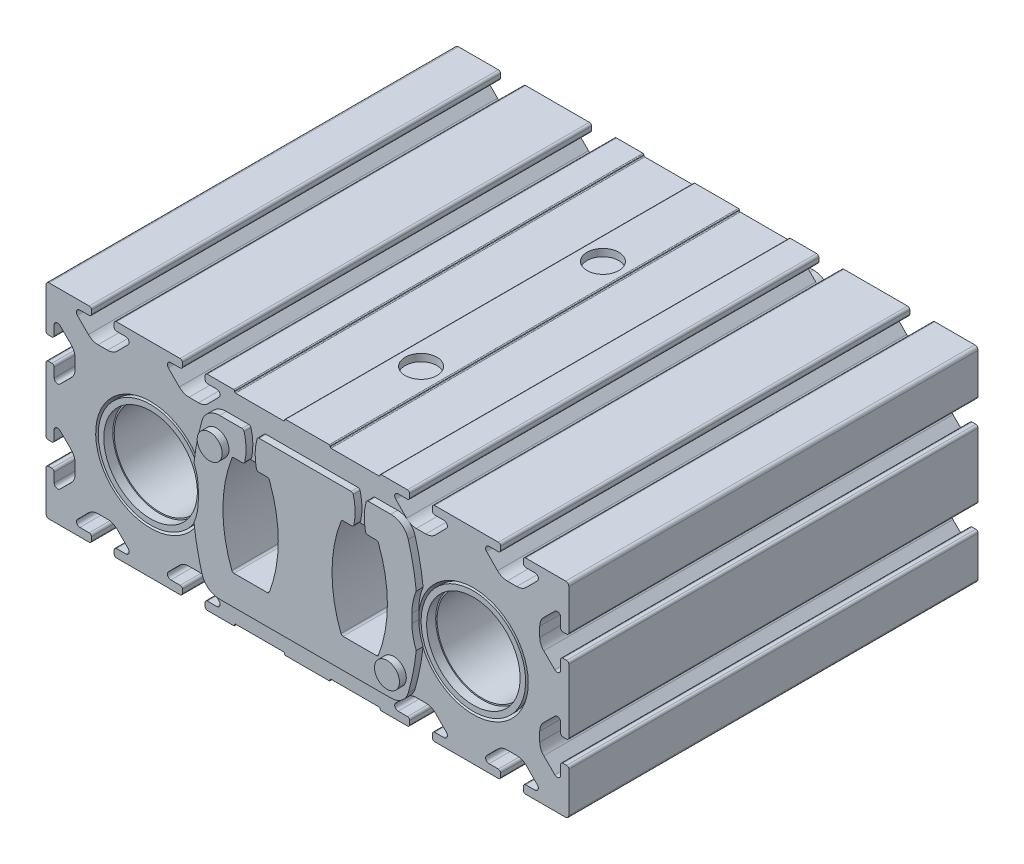
SolidWorks part; units mm, degrees
ref_plane "Front Plane" through (0, 0, 0) normal (0, 0, 1) x (1, 0, 0)
ref_plane "Top Plane" through (0, 0, 0) normal (0, 1, 0) x (1, 0, 0)
ref_plane "Right Plane" through (0, 0, 0) normal (1, 0, 0) x (0, 0, -1)
sketch "Sketch1" plane through (0, 0, 0) normal (0, 0, 1) x (1, 0, 0)
  line L0 (-56.8, -22.5) -> (-48, -22.5)
  line L1 (-47.5, -22) -> (-47.5, -21.2)
  line L2 (-48, -20.7) -> (-50.05, -20.7)
  line L3 (-50.5835, -19.4228) -> (-48.1808, -16.9914)
  line L4 (-46.0469, -16.1) -> (-43.9531, -16.1)
  line L5 (-41.8192, -16.9914) -> (-39.4165, -19.4228)
  line L6 (-39.95, -20.7) -> (-42, -20.7)
  line L7 (-42.5, -21.2) -> (-42.5, -22)
  line L8 (-42, -22.5) -> (-28, -22.5)
  line L9 (-27.5, -22) -> (-27.5, -21.2)
  line L10 (-28, -20.7) -> (-30.05, -20.7)
  line L11 (-30.5835, -19.4228) -> (-28.1808, -16.9914)
  line L12 (-26.0469, -16.1) -> (-23.9531, -16.1)
  line L13 (-21.8192, -16.9914) -> (-19.4165, -19.4228)
  line L14 (-19.95, -20.7) -> (-22, -20.7)
  line L15 (-22.5, -21.2) -> (-22.5, -22)
  line L16 (-22, -22.5) -> (-16.2, -22.5)
  line L17 (-16, -22.3) -> (-16, -22.2)
  line L18 (-15.8, -22) -> (-5.2, -22)
  line L19 (-5, -22.2) -> (-5, -22.3)
  line L20 (-4.8, -22.5) -> (4.8, -22.5)
  line L21 (5, -22.3) -> (5, -22.2)
  line L22 (5.2, -22) -> (15.8, -22)
  line L23 (16, -22.2) -> (16, -22.3)
  line L24 (16.2, -22.5) -> (22, -22.5)
  line L25 (22.5, -22) -> (22.5, -21.2)
  line L26 (22, -20.7) -> (19.95, -20.7)
  line L27 (19.4165, -19.4228) -> (21.8192, -16.9914)
  line L28 (23.9531, -16.1) -> (26.0469, -16.1)
  line L29 (28.1808, -16.9914) -> (30.5835, -19.4228)
  line L30 (30.05, -20.7) -> (28, -20.7)
  line L31 (27.5, -21.2) -> (27.5, -22)
  line L32 (28, -22.5) -> (42, -22.5)
  line L33 (42.5, -22) -> (42.5, -21.2)
  line L34 (42, -20.7) -> (39.95, -20.7)
  line L35 (39.4165, -19.4228) -> (41.8192, -16.9914)
  line L36 (43.9531, -16.1) -> (46.0469, -16.1)
  line L37 (48.1808, -16.9914) -> (50.5835, -19.4228)
  line L38 (50.05, -20.7) -> (48, -20.7)
  line L39 (47.5, -21.2) -> (47.5, -22)
  line L40 (48, -22.5) -> (56.8, -22.5)
  line L41 (57.5, -21.8) -> (57.5, -13)
  line L42 (57, -12.5) -> (56.2, -12.5)
  line L43 (55.7, -13) -> (55.7, -15.05)
  line L44 (54.4228, -15.5835) -> (51.9914, -13.1808)
  line L45 (51.1, -11.0469) -> (51.1, -8.9531)
  line L46 (51.9914, -6.8192) -> (54.4228, -4.4165)
  line L47 (55.7, -4.95) -> (55.7, -7)
  line L48 (56.2, -7.5) -> (57, -7.5)
  line L49 (57.5, -7) -> (57.5, 7)
  line L50 (57, 7.5) -> (56.2, 7.5)
  line L51 (55.7, 7) -> (55.7, 4.95)
  line L52 (54.4228, 4.4165) -> (51.9914, 6.8192)
  line L53 (51.1, 8.9531) -> (51.1, 11.0469)
  line L54 (51.9914, 13.1808) -> (54.4228, 15.5835)
  line L55 (55.7, 15.05) -> (55.7, 13)
  line L56 (56.2, 12.5) -> (57, 12.5)
  line L57 (57.5, 13) -> (57.5, 21.8)
  line L58 (56.8, 22.5) -> (48, 22.5)
  line L59 (47.5, 22) -> (47.5, 21.2)
  line L60 (48, 20.7) -> (50.05, 20.7)
  line L61 (50.5835, 19.4228) -> (48.1808, 16.9914)
  line L62 (46.0469, 16.1) -> (43.9531, 16.1)
  line L63 (41.8192, 16.9914) -> (39.4165, 19.4228)
  line L64 (39.95, 20.7) -> (42, 20.7)
  line L65 (42.5, 21.2) -> (42.5, 22)
  line L66 (42, 22.5) -> (28, 22.5)
  line L67 (27.5, 22) -> (27.5, 21.2)
  line L68 (28, 20.7) -> (30.05, 20.7)
  line L69 (30.5835, 19.4228) -> (28.1808, 16.9914)
  line L70 (26.0469, 16.1) -> (23.9531, 16.1)
  line L71 (21.8192, 16.9914) -> (19.4165, 19.4228)
  line L72 (19.95, 20.7) -> (22, 20.7)
  line L73 (22.5, 21.2) -> (22.5, 22)
  line L74 (22, 22.5) -> (16.2, 22.5)
  line L75 (16, 22.3) -> (16, 22.2)
  line L76 (15.8, 22) -> (5.2, 22)
  line L77 (5, 22.2) -> (5, 22.3)
  line L78 (4.8, 22.5) -> (-4.8, 22.5)
  line L79 (-5, 22.3) -> (-5, 22.2)
  line L80 (-5.2, 22) -> (-15.8, 22)
  line L81 (-16, 22.2) -> (-16, 22.3)
  line L82 (-16.2, 22.5) -> (-22, 22.5)
  line L83 (-22.5, 22) -> (-22.5, 21.2)
  line L84 (-22, 20.7) -> (-19.95, 20.7)
  line L85 (-19.4165, 19.4228) -> (-21.8192, 16.9914)
  line L86 (-23.9531, 16.1) -> (-26.0469, 16.1)
  line L87 (-28.1808, 16.9914) -> (-30.5835, 19.4228)
  line L88 (-30.05, 20.7) -> (-28, 20.7)
  line L89 (-27.5, 21.2) -> (-27.5, 22)
  line L90 (-28, 22.5) -> (-42, 22.5)
  line L91 (-42.5, 22) -> (-42.5, 21.2)
  line L92 (-42, 20.7) -> (-39.95, 20.7)
  line L93 (-39.4165, 19.4228) -> (-41.8192, 16.9914)
  line L94 (-43.9531, 16.1) -> (-46.0469, 16.1)
  line L95 (-48.1808, 16.9914) -> (-50.5835, 19.4228)
  line L96 (-50.05, 20.7) -> (-48, 20.7)
  line L97 (-47.5, 21.2) -> (-47.5, 22)
  line L98 (-48, 22.5) -> (-56.8, 22.5)
  line L99 (-57.5, 21.8) -> (-57.5, 13)
  line L100 (-57, 12.5) -> (-56.2, 12.5)
  line L101 (-55.7, 13) -> (-55.7, 15.05)
  line L102 (-54.4228, 15.5835) -> (-51.9914, 13.1808)
  line L103 (-51.1, 11.0469) -> (-51.1, 8.9531)
  line L104 (-51.9914, 6.8192) -> (-54.4228, 4.4165)
  line L105 (-55.7, 4.95) -> (-55.7, 7)
  line L106 (-56.2, 7.5) -> (-57, 7.5)
  line L107 (-57.5, 7) -> (-57.5, -7)
  line L108 (-57, -7.5) -> (-56.2, -7.5)
  line L109 (-55.7, -7) -> (-55.7, -4.95)
  line L110 (-54.4228, -4.4165) -> (-51.9914, -6.8192)
  line L111 (-51.1, -8.9531) -> (-51.1, -11.0469)
  line L112 (-51.9914, -13.1808) -> (-54.4228, -15.5835)
  line L113 (-55.7, -15.05) -> (-55.7, -13)
  line L114 (-56.2, -12.5) -> (-57, -12.5)
  line L115 (-57.5, -13) -> (-57.5, -21.8)
  line L116 (9.3425, -11) -> (16.6575, -11)
  line L117 (16.6575, 11) -> (9.3425, 11)
  line L118 (-14.6575, -11) -> (-7.3425, -11)
  line L119 (-7.3425, 11) -> (-14.6575, 11)
  arc A0 (-57.5, -21.8) -> (-56.8, -22.5) centre (-56.8, -21.8) ccw
  arc A1 (-48, -22.5) -> (-47.5, -22) centre (-48, -22) ccw
  arc A2 (-47.5, -21.2) -> (-48, -20.7) centre (-48, -21.2) ccw
  arc A3 (-50.05, -20.7) -> (-50.5835, -19.4228) centre (-50.05, -19.95) cw
  arc A4 (-48.1808, -16.9914) -> (-46.0469, -16.1) centre (-46.0469, -19.1) cw
  arc A5 (-43.9531, -16.1) -> (-41.8192, -16.9914) centre (-43.9531, -19.1) cw
  arc A6 (-39.4165, -19.4228) -> (-39.95, -20.7) centre (-39.95, -19.95) cw
  arc A7 (-42, -20.7) -> (-42.5, -21.2) centre (-42, -21.2) ccw
  arc A8 (-42.5, -22) -> (-42, -22.5) centre (-42, -22) ccw
  arc A9 (-28, -22.5) -> (-27.5, -22) centre (-28, -22) ccw
  arc A10 (-27.5, -21.2) -> (-28, -20.7) centre (-28, -21.2) ccw
  arc A11 (-30.05, -20.7) -> (-30.5835, -19.4228) centre (-30.05, -19.95) cw
  arc A12 (-28.1808, -16.9914) -> (-26.0469, -16.1) centre (-26.0469, -19.1) cw
  arc A13 (-23.9531, -16.1) -> (-21.8192, -16.9914) centre (-23.9531, -19.1) cw
  arc A14 (-19.4165, -19.4228) -> (-19.95, -20.7) centre (-19.95, -19.95) cw
  arc A15 (-22, -20.7) -> (-22.5, -21.2) centre (-22, -21.2) ccw
  arc A16 (-22.5, -22) -> (-22, -22.5) centre (-22, -22) ccw
  arc A17 (-16.2, -22.5) -> (-16, -22.3) centre (-16.2, -22.3) ccw
  arc A18 (-16, -22.2) -> (-15.8, -22) centre (-15.8, -22.2) cw
  arc A19 (-5.2, -22) -> (-5, -22.2) centre (-5.2, -22.2) cw
  arc A20 (-5, -22.3) -> (-4.8, -22.5) centre (-4.8, -22.3) ccw
  arc A21 (4.8, -22.5) -> (5, -22.3) centre (4.8, -22.3) ccw
  arc A22 (5, -22.2) -> (5.2, -22) centre (5.2, -22.2) cw
  arc A23 (15.8, -22) -> (16, -22.2) centre (15.8, -22.2) cw
  arc A24 (16, -22.3) -> (16.2, -22.5) centre (16.2, -22.3) ccw
  arc A25 (22, -22.5) -> (22.5, -22) centre (22, -22) ccw
  arc A26 (22.5, -21.2) -> (22, -20.7) centre (22, -21.2) ccw
  arc A27 (19.95, -20.7) -> (19.4165, -19.4228) centre (19.95, -19.95) cw
  arc A28 (21.8192, -16.9914) -> (23.9531, -16.1) centre (23.9531, -19.1) cw
  arc A29 (26.0469, -16.1) -> (28.1808, -16.9914) centre (26.0469, -19.1) cw
  arc A30 (30.5835, -19.4228) -> (30.05, -20.7) centre (30.05, -19.95) cw
  arc A31 (28, -20.7) -> (27.5, -21.2) centre (28, -21.2) ccw
  arc A32 (27.5, -22) -> (28, -22.5) centre (28, -22) ccw
  arc A33 (42, -22.5) -> (42.5, -22) centre (42, -22) ccw
  arc A34 (42.5, -21.2) -> (42, -20.7) centre (42, -21.2) ccw
  arc A35 (39.95, -20.7) -> (39.4165, -19.4228) centre (39.95, -19.95) cw
  arc A36 (41.8192, -16.9914) -> (43.9531, -16.1) centre (43.9531, -19.1) cw
  arc A37 (46.0469, -16.1) -> (48.1808, -16.9914) centre (46.0469, -19.1) cw
  arc A38 (50.5835, -19.4228) -> (50.05, -20.7) centre (50.05, -19.95) cw
  arc A39 (48, -20.7) -> (47.5, -21.2) centre (48, -21.2) ccw
  arc A40 (47.5, -22) -> (48, -22.5) centre (48, -22) ccw
  arc A41 (56.8, -22.5) -> (57.5, -21.8) centre (56.8, -21.8) ccw
  arc A42 (57.5, -13) -> (57, -12.5) centre (57, -13) ccw
  arc A43 (56.2, -12.5) -> (55.7, -13) centre (56.2, -13) ccw
  arc A44 (55.7, -15.05) -> (54.4228, -15.5835) centre (54.95, -15.05) cw
  arc A45 (51.9914, -13.1808) -> (51.1, -11.0469) centre (54.1, -11.0469) cw
  arc A46 (51.1, -8.9531) -> (51.9914, -6.8192) centre (54.1, -8.9531) cw
  arc A47 (54.4228, -4.4165) -> (55.7, -4.95) centre (54.95, -4.95) cw
  arc A48 (55.7, -7) -> (56.2, -7.5) centre (56.2, -7) ccw
  arc A49 (57, -7.5) -> (57.5, -7) centre (57, -7) ccw
  arc A50 (57.5, 7) -> (57, 7.5) centre (57, 7) ccw
  arc A51 (56.2, 7.5) -> (55.7, 7) centre (56.2, 7) ccw
  arc A52 (55.7, 4.95) -> (54.4228, 4.4165) centre (54.95, 4.95) cw
  arc A53 (51.9914, 6.8192) -> (51.1, 8.9531) centre (54.1, 8.9531) cw
  arc A54 (51.1, 11.0469) -> (51.9914, 13.1808) centre (54.1, 11.0469) cw
  arc A55 (54.4228, 15.5835) -> (55.7, 15.05) centre (54.95, 15.05) cw
  arc A56 (55.7, 13) -> (56.2, 12.5) centre (56.2, 13) ccw
  arc A57 (57, 12.5) -> (57.5, 13) centre (57, 13) ccw
  arc A58 (57.5, 21.8) -> (56.8, 22.5) centre (56.8, 21.8) ccw
  arc A59 (48, 22.5) -> (47.5, 22) centre (48, 22) ccw
  arc A60 (47.5, 21.2) -> (48, 20.7) centre (48, 21.2) ccw
  arc A61 (50.05, 20.7) -> (50.5835, 19.4228) centre (50.05, 19.95) cw
  arc A62 (48.1808, 16.9914) -> (46.0469, 16.1) centre (46.0469, 19.1) cw
  arc A63 (43.9531, 16.1) -> (41.8192, 16.9914) centre (43.9531, 19.1) cw
  arc A64 (39.4165, 19.4228) -> (39.95, 20.7) centre (39.95, 19.95) cw
  arc A65 (42, 20.7) -> (42.5, 21.2) centre (42, 21.2) ccw
  arc A66 (42.5, 22) -> (42, 22.5) centre (42, 22) ccw
  arc A67 (28, 22.5) -> (27.5, 22) centre (28, 22) ccw
  arc A68 (27.5, 21.2) -> (28, 20.7) centre (28, 21.2) ccw
  arc A69 (30.05, 20.7) -> (30.5835, 19.4228) centre (30.05, 19.95) cw
  arc A70 (28.1808, 16.9914) -> (26.0469, 16.1) centre (26.0469, 19.1) cw
  arc A71 (23.9531, 16.1) -> (21.8192, 16.9914) centre (23.9531, 19.1) cw
  arc A72 (19.4165, 19.4228) -> (19.95, 20.7) centre (19.95, 19.95) cw
  arc A73 (22, 20.7) -> (22.5, 21.2) centre (22, 21.2) ccw
  arc A74 (22.5, 22) -> (22, 22.5) centre (22, 22) ccw
  arc A75 (16.2, 22.5) -> (16, 22.3) centre (16.2, 22.3) ccw
  arc A76 (16, 22.2) -> (15.8, 22) centre (15.8, 22.2) cw
  arc A77 (5.2, 22) -> (5, 22.2) centre (5.2, 22.2) cw
  arc A78 (5, 22.3) -> (4.8, 22.5) centre (4.8, 22.3) ccw
  arc A79 (-4.8, 22.5) -> (-5, 22.3) centre (-4.8, 22.3) ccw
  arc A80 (-5, 22.2) -> (-5.2, 22) centre (-5.2, 22.2) cw
  arc A81 (-15.8, 22) -> (-16, 22.2) centre (-15.8, 22.2) cw
  arc A82 (-16, 22.3) -> (-16.2, 22.5) centre (-16.2, 22.3) ccw
  arc A83 (-22, 22.5) -> (-22.5, 22) centre (-22, 22) ccw
  arc A84 (-22.5, 21.2) -> (-22, 20.7) centre (-22, 21.2) ccw
  arc A85 (-19.95, 20.7) -> (-19.4165, 19.4228) centre (-19.95, 19.95) cw
  arc A86 (-21.8192, 16.9914) -> (-23.9531, 16.1) centre (-23.9531, 19.1) cw
  arc A87 (-26.0469, 16.1) -> (-28.1808, 16.9914) centre (-26.0469, 19.1) cw
  arc A88 (-30.5835, 19.4228) -> (-30.05, 20.7) centre (-30.05, 19.95) cw
  arc A89 (-28, 20.7) -> (-27.5, 21.2) centre (-28, 21.2) ccw
  arc A90 (-27.5, 22) -> (-28, 22.5) centre (-28, 22) ccw
  arc A91 (-42, 22.5) -> (-42.5, 22) centre (-42, 22) ccw
  arc A92 (-42.5, 21.2) -> (-42, 20.7) centre (-42, 21.2) ccw
  arc A93 (-39.95, 20.7) -> (-39.4165, 19.4228) centre (-39.95, 19.95) cw
  arc A94 (-41.8192, 16.9914) -> (-43.9531, 16.1) centre (-43.9531, 19.1) cw
  arc A95 (-46.0469, 16.1) -> (-48.1808, 16.9914) centre (-46.0469, 19.1) cw
  arc A96 (-50.5835, 19.4228) -> (-50.05, 20.7) centre (-50.05, 19.95) cw
  arc A97 (-48, 20.7) -> (-47.5, 21.2) centre (-48, 21.2) ccw
  arc A98 (-47.5, 22) -> (-48, 22.5) centre (-48, 22) ccw
  arc A99 (-56.8, 22.5) -> (-57.5, 21.8) centre (-56.8, 21.8) ccw
  arc A100 (-57.5, 13) -> (-57, 12.5) centre (-57, 13) ccw
  arc A101 (-56.2, 12.5) -> (-55.7, 13) centre (-56.2, 13) ccw
  arc A102 (-55.7, 15.05) -> (-54.4228, 15.5835) centre (-54.95, 15.05) cw
  arc A103 (-51.9914, 13.1808) -> (-51.1, 11.0469) centre (-54.1, 11.0469) cw
  arc A104 (-51.1, 8.9531) -> (-51.9914, 6.8192) centre (-54.1, 8.9531) cw
  arc A105 (-54.4228, 4.4165) -> (-55.7, 4.95) centre (-54.95, 4.95) cw
  arc A106 (-55.7, 7) -> (-56.2, 7.5) centre (-56.2, 7) ccw
  arc A107 (-57, 7.5) -> (-57.5, 7) centre (-57, 7) ccw
  arc A108 (-57.5, -7) -> (-57, -7.5) centre (-57, -7) ccw
  arc A109 (-56.2, -7.5) -> (-55.7, -7) centre (-56.2, -7) ccw
  arc A110 (-55.7, -4.95) -> (-54.4228, -4.4165) centre (-54.95, -4.95) cw
  arc A111 (-51.9914, -6.8192) -> (-51.1, -8.9531) centre (-54.1, -8.9531) cw
  arc A112 (-51.1, -11.0469) -> (-51.9914, -13.1808) centre (-54.1, -11.0469) cw
  arc A113 (-54.4228, -15.5835) -> (-55.7, -15.05) centre (-54.95, -15.05) cw
  arc A114 (-55.7, -13) -> (-56.2, -12.5) centre (-56.2, -13) ccw
  arc A115 (-57, -12.5) -> (-57.5, -13) centre (-57, -13) ccw
  arc A116 (8.8752, 10.678) -> (8.8752, -10.678) centre (36.9106, 0) ccw
  arc A117 (8.8752, -10.678) -> (9.3425, -11) centre (9.3425, -10.5) ccw
  arc A118 (16.6575, -11) -> (17.1248, -10.678) centre (16.6575, -10.5) ccw
  arc A119 (17.1248, -10.678) -> (17.1248, 10.678) centre (-10.9106, 0) ccw
  arc A120 (17.1248, 10.678) -> (16.6575, 11) centre (16.6575, 10.5) ccw
  arc A121 (9.3425, 11) -> (8.8752, 10.678) centre (9.3425, 10.5) ccw
  arc A122 (-15.1248, 10.678) -> (-15.1248, -10.678) centre (12.9106, 0) ccw
  arc A123 (-15.1248, -10.678) -> (-14.6575, -11) centre (-14.6575, -10.5) ccw
  arc A124 (-7.3425, -11) -> (-6.8752, -10.678) centre (-7.3425, -10.5) ccw
  arc A125 (-6.8752, -10.678) -> (-6.8752, 10.678) centre (-34.9106, 0) ccw
  arc A126 (-6.8752, 10.678) -> (-7.3425, 11) centre (-7.3425, 10.5) ccw
  arc A127 (-14.6575, 11) -> (-15.1248, 10.678) centre (-14.6575, 10.5) ccw
extrude "Boss-Extrude1" add sketch "Sketch1" against normal blind 90
ref_plane "Plane4" through (0, -1, 0) normal (0, 1, 0) x (1, 0, 0)
sketch "Sketch2" plane through (0, -1, 0) normal (0, 1, 0) x (1, 0, 0)
  line L0 (-34.5, 90) -> (-22.4226, 90)
  line L1 (-22.4226, 90) -> (-23, 89)
  line L2 (-23, 89) -> (-23, 1)
  line L3 (-23, 1) -> (-22.4226, 0)
  line L4 (-22.4226, 0) -> (-34.5, 0)
  line L5 (-34.5, 0) -> (-34.5, 90)
  line L6 (-34.5, 0) -> (-34.5, 90) construction
revolve "Cut-Revolve1" cut sketch "Sketch2" angle 360 about L6 reverse direction yes
sketch "Sketch3" plane through (0, -1, 0) normal (0, 1, 0) x (1, 0, 0)
  line L0 (36.5, 90) -> (48.5774, 90)
  line L1 (48.5774, 90) -> (48, 89)
  line L2 (48, 89) -> (48, 1)
  line L3 (48, 1) -> (48.5774, 0)
  line L4 (48.5774, 0) -> (36.5, 0)
  line L5 (36.5, 0) -> (36.5, 90)
  line L6 (36.5, 0) -> (36.5, 90) construction
revolve "Cut-Revolve2" cut sketch "Sketch3" angle 360 about L6 reverse direction yes
sketch "Sketch4" plane through (0, -1, 0) normal (0, 1, 0) x (1, 0, 0)
  line L0 (-24.5, 2) -> (-24.21, 2)
  line L1 (-24.21, 2) -> (-24.21, 0)
  line L2 (-24.21, 0) -> (-23, 0)
  line L3 (-23, 0) -> (-23, 24.2)
  line L4 (-23, 24.2) -> (-23.4619, 25)
  line L5 (-23.4619, 25) -> (-24.5, 25)
  line L6 (-24.5, 25) -> (-24.5, 2)
  line L7 (-34.5, 0) -> (-34.5, 25) construction
revolve "Revolve1" add sketch "Sketch4" angle 360 about L7 reverse direction yes
sketch "Sketch5" plane through (0, -1, 0) normal (0, 1, 0) x (1, 0, 0)
  line L0 (46.5, 2) -> (46.79, 2)
  line L1 (46.79, 2) -> (46.79, 0)
  line L2 (46.79, 0) -> (48, 0)
  line L3 (48, 0) -> (48, 24.2)
  line L4 (48, 24.2) -> (47.5381, 25)
  line L5 (47.5381, 25) -> (46.5, 25)
  line L6 (46.5, 25) -> (46.5, 2)
  line L7 (36.5, 0) -> (36.5, 25) construction
revolve "Revolve2" add sketch "Sketch5" angle 360 about L7 reverse direction yes
sketch "Sketch6" plane through (0, -1, 0) normal (0, 1, 0) x (1, 0, 0)
  line L0 (46.5, 88) -> (46.5, 65)
  line L1 (46.5, 65) -> (47.5381, 65)
  line L2 (47.5381, 65) -> (48, 65.8)
  line L3 (48, 65.8) -> (48, 90)
  line L4 (48, 90) -> (46.79, 90)
  line L5 (46.79, 90) -> (46.79, 88)
  line L6 (46.79, 88) -> (46.5, 88)
  line L7 (36.5, 65) -> (36.5, 90) construction
revolve "Revolve3" add sketch "Sketch6" angle 360 about L7 reverse direction yes
sketch "Sketch7" plane through (0, -1, 0) normal (0, 1, 0) x (1, 0, 0)
  line L0 (-24.5, 88) -> (-24.5, 65)
  line L1 (-24.5, 65) -> (-23.4619, 65)
  line L2 (-23.4619, 65) -> (-23, 65.8)
  line L3 (-23, 65.8) -> (-23, 90)
  line L4 (-23, 90) -> (-24.21, 90)
  line L5 (-24.21, 90) -> (-24.21, 88)
  line L6 (-24.21, 88) -> (-24.5, 88)
  line L7 (-34.5, 65) -> (-34.5, 90) construction
revolve "Revolve4" add sketch "Sketch7" angle 360 about L7 reverse direction yes
sketch "Sketch8" plane through (0, 0, 0) normal (0, 0, 1) x (1, 0, 0)
  line L0 (-22.5, 1) -> (-22.5, -1)
  line L1 (-17.8333, -17.5) -> (19.8333, -17.5)
  line L2 (24.5, -1) -> (24.5, 1)
  line L3 (19.8333, 17.5) -> (14.8982, 17.5)
  line L4 (14.775, 11) -> (16.6575, 11)
  line L5 (16.6575, -11) -> (9.3425, -11)
  line L6 (9.3425, 11) -> (11.225, 11)
  line L7 (11.1018, 17.5) -> (-9.1018, 17.5)
  line L8 (-9.225, 11) -> (-7.3425, 11)
  line L9 (-7.3425, -11) -> (-14.6575, -11)
  line L10 (-14.6575, 11) -> (-12.775, 11)
  line L11 (-12.8982, 17.5) -> (-17.8333, 17.5)
  arc A0 (-23.4435, 5.6642) -> (-22.5, 1) centre (-34.5, 1) cw
  arc A1 (-22.5, -1) -> (-23.4435, -5.6642) centre (-34.5, -1) cw
  arc A2 (-23.4435, -5.6642) -> (-21.6752, -14.6134) centre (28.75, 0) ccw
  arc A3 (-21.6752, -14.6134) -> (-17.8333, -17.5) centre (-17.8333, -13.5) ccw
  arc A4 (19.8333, -17.5) -> (23.6752, -14.6134) centre (19.8333, -13.5) ccw
  arc A5 (23.6752, -14.6134) -> (25.4435, -5.6642) centre (-26.75, 0) ccw
  arc A6 (25.4435, -5.6642) -> (24.5, -1) centre (36.5, -1) cw
  arc A7 (24.5, 1) -> (25.4435, 5.6642) centre (36.5, 1) cw
  arc A8 (25.4435, 5.6642) -> (23.6752, 14.6134) centre (-26.75, 0) ccw
  arc A9 (23.6752, 14.6134) -> (19.8333, 17.5) centre (19.8333, 13.5) ccw
  arc A10 (14.8982, 17.5) -> (14.4155, 17.1304) centre (14.8982, 17) ccw
  arc A11 (14.4155, 17.1304) -> (14.287, 11.3913) centre (26, 14) ccw
  arc A12 (14.287, 11.3913) -> (14.775, 11) centre (14.775, 11.5) ccw
  arc A13 (16.6575, 11) -> (17.1248, 10.678) centre (16.6575, 10.5) cw
  arc A14 (17.1248, 10.678) -> (17.1248, -10.678) centre (-10.9106, 0) cw
  arc A15 (17.1248, -10.678) -> (16.6575, -11) centre (16.6575, -10.5) cw
  arc A16 (9.3425, -11) -> (8.8752, -10.678) centre (9.3425, -10.5) cw
  arc A17 (8.8752, -10.678) -> (8.8752, 10.678) centre (36.9106, 0) cw
  arc A18 (8.8752, 10.678) -> (9.3425, 11) centre (9.3425, 10.5) cw
  arc A19 (11.225, 11) -> (11.713, 11.3913) centre (11.225, 11.5) ccw
  arc A20 (11.713, 11.3913) -> (11.5845, 17.1304) centre (0, 14) ccw
  arc A21 (11.5845, 17.1304) -> (11.1018, 17.5) centre (11.1018, 17) ccw
  arc A22 (-9.1018, 17.5) -> (-9.5845, 17.1304) centre (-9.1018, 17) ccw
  arc A23 (-9.5845, 17.1304) -> (-9.713, 11.3913) centre (2, 14) ccw
  arc A24 (-9.713, 11.3913) -> (-9.225, 11) centre (-9.225, 11.5) ccw
  arc A25 (-7.3425, 11) -> (-6.8752, 10.678) centre (-7.3425, 10.5) cw
  arc A26 (-6.8752, 10.678) -> (-6.8752, -10.678) centre (-34.9106, 0) cw
  arc A27 (-6.8752, -10.678) -> (-7.3425, -11) centre (-7.3425, -10.5) cw
  arc A28 (-14.6575, -11) -> (-15.1248, -10.678) centre (-14.6575, -10.5) cw
  arc A29 (-15.1248, -10.678) -> (-15.1248, 10.678) centre (12.9106, 0) cw
  arc A30 (-15.1248, 10.678) -> (-14.6575, 11) centre (-14.6575, 10.5) cw
  arc A31 (-12.775, 11) -> (-12.287, 11.3913) centre (-12.775, 11.5) ccw
  arc A32 (-12.287, 11.3913) -> (-12.4155, 17.1304) centre (-24, 14) ccw
  arc A33 (-12.4155, 17.1304) -> (-12.8982, 17.5) centre (-12.8982, 17) ccw
  arc A34 (-17.8333, 17.5) -> (-21.6752, 14.6134) centre (-17.8333, 13.5) ccw
  arc A35 (-21.6752, 14.6134) -> (-23.4435, 5.6642) centre (28.75, 0) ccw
  circle A36 centre (20.5, -12) radius 1.5
  circle A37 centre (-18.5, 12) radius 1.5
extrude "Boss-Extrude2" add sketch "Sketch8" along normal blind 1.5
ref_plane "Plane5" through (0, 0, -90) normal (0, 0, 1) x (1, 0, 0)
sketch "Sketch9" plane through (0, 0, -90) normal (0, 0, 1) x (1, 0, 0)
  line L0 (-22.5, 1) -> (-22.5, -1)
  line L1 (-17.8333, -17.5) -> (19.8333, -17.5)
  line L2 (24.5, -1) -> (24.5, 1)
  line L3 (19.8333, 17.5) -> (14.8982, 17.5)
  line L4 (14.775, 11) -> (16.6575, 11)
  line L5 (16.6575, -11) -> (9.3425, -11)
  line L6 (9.3425, 11) -> (11.225, 11)
  line L7 (11.1018, 17.5) -> (-9.1018, 17.5)
  line L8 (-9.225, 11) -> (-7.3425, 11)
  line L9 (-7.3425, -11) -> (-14.6575, -11)
  line L10 (-14.6575, 11) -> (-12.775, 11)
  line L11 (-12.8982, 17.5) -> (-17.8333, 17.5)
  arc A0 (-23.4435, 5.6642) -> (-22.5, 1) centre (-34.5, 1) cw
  arc A1 (-22.5, -1) -> (-23.4435, -5.6642) centre (-34.5, -1) cw
  arc A2 (-23.4435, -5.6642) -> (-21.6752, -14.6134) centre (28.75, 0) ccw
  arc A3 (-21.6752, -14.6134) -> (-17.8333, -17.5) centre (-17.8333, -13.5) ccw
  arc A4 (19.8333, -17.5) -> (23.6752, -14.6134) centre (19.8333, -13.5) ccw
  arc A5 (23.6752, -14.6134) -> (25.4435, -5.6642) centre (-26.75, 0) ccw
  arc A6 (25.4435, -5.6642) -> (24.5, -1) centre (36.5, -1) cw
  arc A7 (24.5, 1) -> (25.4435, 5.6642) centre (36.5, 1) cw
  arc A8 (25.4435, 5.6642) -> (23.6752, 14.6134) centre (-26.75, 0) ccw
  arc A9 (23.6752, 14.6134) -> (19.8333, 17.5) centre (19.8333, 13.5) ccw
  arc A10 (14.8982, 17.5) -> (14.4155, 17.1304) centre (14.8982, 17) ccw
  arc A11 (14.4155, 17.1304) -> (14.287, 11.3913) centre (26, 14) ccw
  arc A12 (14.287, 11.3913) -> (14.775, 11) centre (14.775, 11.5) ccw
  arc A13 (16.6575, 11) -> (17.1248, 10.678) centre (16.6575, 10.5) cw
  arc A14 (17.1248, 10.678) -> (17.1248, -10.678) centre (-10.9106, 0) cw
  arc A15 (17.1248, -10.678) -> (16.6575, -11) centre (16.6575, -10.5) cw
  arc A16 (9.3425, -11) -> (8.8752, -10.678) centre (9.3425, -10.5) cw
  arc A17 (8.8752, -10.678) -> (8.8752, 10.678) centre (36.9106, 0) cw
  arc A18 (8.8752, 10.678) -> (9.3425, 11) centre (9.3425, 10.5) cw
  arc A19 (11.225, 11) -> (11.713, 11.3913) centre (11.225, 11.5) ccw
  arc A20 (11.713, 11.3913) -> (11.5845, 17.1304) centre (0, 14) ccw
  arc A21 (11.5845, 17.1304) -> (11.1018, 17.5) centre (11.1018, 17) ccw
  arc A22 (-9.1018, 17.5) -> (-9.5845, 17.1304) centre (-9.1018, 17) ccw
  arc A23 (-9.5845, 17.1304) -> (-9.713, 11.3913) centre (2, 14) ccw
  arc A24 (-9.713, 11.3913) -> (-9.225, 11) centre (-9.225, 11.5) ccw
  arc A25 (-7.3425, 11) -> (-6.8752, 10.678) centre (-7.3425, 10.5) cw
  arc A26 (-6.8752, 10.678) -> (-6.8752, -10.678) centre (-34.9106, 0) cw
  arc A27 (-6.8752, -10.678) -> (-7.3425, -11) centre (-7.3425, -10.5) cw
  arc A28 (-14.6575, -11) -> (-15.1248, -10.678) centre (-14.6575, -10.5) cw
  arc A29 (-15.1248, -10.678) -> (-15.1248, 10.678) centre (12.9106, 0) cw
  arc A30 (-15.1248, 10.678) -> (-14.6575, 11) centre (-14.6575, 10.5) cw
  arc A31 (-12.775, 11) -> (-12.287, 11.3913) centre (-12.775, 11.5) ccw
  arc A32 (-12.287, 11.3913) -> (-12.4155, 17.1304) centre (-24, 14) ccw
  arc A33 (-12.4155, 17.1304) -> (-12.8982, 17.5) centre (-12.8982, 17) ccw
  arc A34 (-17.8333, 17.5) -> (-21.6752, 14.6134) centre (-17.8333, 13.5) ccw
  arc A35 (-21.6752, 14.6134) -> (-23.4435, 5.6642) centre (28.75, 0) ccw
  circle A36 centre (20.5, -12) radius 1.5
  circle A37 centre (-18.5, 12) radius 1.5
extrude "Boss-Extrude3" add sketch "Sketch9" against normal blind 1.5
ref_plane "Plane6" through (-18.5, 0, 0) normal (1, 0, 0) x (0, 0, -1)
sketch "Sketch10" plane through (-18.5, 0, 0) normal (1, 0, 0) x (0, 0, -1)
  line L0 (74.4, 12) -> (74.4, 12.5)
  line L1 (74.4, 12.5) -> (74.9, 13)
  line L2 (74.9, 13) -> (77, 13)
  line L3 (77, 13) -> (77, 13.1)
  line L4 (77, 13.1) -> (77.5, 13.6)
  line L5 (77.5, 13.6) -> (91.5, 13.6)
  line L6 (91.5, 13.6) -> (91.5, 14.75)
  line L7 (91.5, 14.75) -> (93, 14.75)
  line L8 (93, 14.75) -> (93, 12)
  line L9 (93, 12) -> (74.4, 12)
  line L10 (93, 12) -> (74.4, 12) construction
revolve "Revolve5" add sketch "Sketch10" angle 360 about L10 reverse direction yes
sketch "Sketch11" plane through (-18.5, 0, 0) normal (1, 0, 0) x (0, 0, -1)
  line L0 (-3, 12) -> (-3, 14.75)
  line L1 (-3, 14.75) -> (-1.5, 14.75)
  line L2 (-1.5, 14.75) -> (-1.5, 13.6)
  line L3 (-1.5, 13.6) -> (12.5, 13.6)
  line L4 (12.5, 13.6) -> (13, 13.1)
  line L5 (13, 13.1) -> (13, 13)
  line L6 (13, 13) -> (15.1, 13)
  line L7 (15.1, 13) -> (15.6, 12.5)
  line L8 (15.6, 12.5) -> (15.6, 12)
  line L9 (15.6, 12) -> (-3, 12)
  line L10 (15.6, 12) -> (-3, 12) construction
revolve "Revolve6" add sketch "Sketch11" angle 360 about L10 reverse direction yes
ref_plane "Plane7" through (20.5, 0, 0) normal (1, 0, 0) x (0, 0, -1)
sketch "Sketch12" plane through (20.5, 0, 0) normal (1, 0, 0) x (0, 0, -1)
  line L0 (-3, -12) -> (-3, -9.25)
  line L1 (-3, -9.25) -> (-1.5, -9.25)
  line L2 (-1.5, -9.25) -> (-1.5, -10.4)
  line L3 (-1.5, -10.4) -> (12.5, -10.4)
  line L4 (12.5, -10.4) -> (13, -10.9)
  line L5 (13, -10.9) -> (13, -11)
  line L6 (13, -11) -> (15.1, -11)
  line L7 (15.1, -11) -> (15.6, -11.5)
  line L8 (15.6, -11.5) -> (15.6, -12)
  line L9 (15.6, -12) -> (-3, -12)
  line L10 (15.6, -12) -> (-3, -12) construction
revolve "Revolve7" add sketch "Sketch12" angle 360 about L10 reverse direction yes
sketch "Sketch13" plane through (20.5, 0, 0) normal (1, 0, 0) x (0, 0, -1)
  line L0 (74.4, -12) -> (74.4, -11.5)
  line L1 (74.4, -11.5) -> (74.9, -11)
  line L2 (74.9, -11) -> (77, -11)
  line L3 (77, -11) -> (77, -10.9)
  line L4 (77, -10.9) -> (77.5, -10.4)
  line L5 (77.5, -10.4) -> (91.5, -10.4)
  line L6 (91.5, -10.4) -> (91.5, -9.25)
  line L7 (91.5, -9.25) -> (93, -9.25)
  line L8 (93, -9.25) -> (93, -12)
  line L9 (93, -12) -> (74.4, -12)
  line L10 (93, -12) -> (74.4, -12) construction
revolve "Revolve8" add sketch "Sketch13" angle 360 about L10 reverse direction yes
sketch "Sketch14" plane through (0, 0, 0) normal (1, 0, 0) x (0, 0, -1)
  line L0 (25, 22.5) -> (28.5, 22.5)
  line L1 (28.5, 22.5) -> (28.5, 20.9)
  line L2 (28.5, 20.9) -> (25, 20.9)
  line L3 (25, 20.9) -> (25, 22.5)
  line L4 (25, 20.9) -> (25, 22.5) construction
revolve "Cut-Revolve3" cut sketch "Sketch14" angle 360 about L4 reverse direction yes
sketch "Sketch15" plane through (0, 0, 0) normal (1, 0, 0) x (0, 0, -1)
  line L0 (65, 22.5) -> (68.5, 22.5)
  line L1 (68.5, 22.5) -> (68.5, 20.9)
  line L2 (68.5, 20.9) -> (65, 20.9)
  line L3 (65, 20.9) -> (65, 22.5)
  line L4 (65, 20.9) -> (65, 22.5) construction
revolve "Cut-Revolve4" cut sketch "Sketch15" angle 360 about L4 reverse direction yes
sketch "Sketch16" plane through (0, 0, 0) normal (0, 1, 0) x (1, 0, 0)
  line L0 (-57.5, 25) -> (-57.5, 28.5)
  line L1 (-57.5, 28.5) -> (-55.9, 28.5)
  line L2 (-55.9, 28.5) -> (-55.9, 25)
  line L3 (-55.9, 25) -> (-57.5, 25)
  line L4 (-55.9, 25) -> (-57.5, 25) construction
revolve "Cut-Revolve5" cut sketch "Sketch16" angle 360 about L4 reverse direction yes
sketch "Sketch17" plane through (0, 0, 0) normal (0, 1, 0) x (1, 0, 0)
  line L0 (-57.5, 65) -> (-57.5, 68.5)
  line L1 (-57.5, 68.5) -> (-55.9, 68.5)
  line L2 (-55.9, 68.5) -> (-55.9, 65)
  line L3 (-55.9, 65) -> (-57.5, 65)
  line L4 (-55.9, 65) -> (-57.5, 65) construction
revolve "Cut-Revolve6" cut sketch "Sketch17" angle 360 about L4 reverse direction yes
ref_plane "Plane8" through (-3.3, 0, 0) normal (1, 0, 0) x (0, 0, -1)
ref_plane "Plane9" through (0, 0, -45) normal (0, 0, 1) x (1, 0, 0)
ref_plane "SCHLITTEN_KURTZ XY" through (0, 0, -45) normal (0, 0, -1) x (-1, 0, 0)
ref_plane "SCHLITTEN_KURTZ XZ" through (0, -2, 0) normal (0, 1, 0) x (1, 0, 0)
ref_plane "SCHLITTEN_KURTZ YZ" through (2, 0, 0) normal (1, 0, 0) x (0, 0, -1)
ref_axis "SCHLITTEN_KURTZ X" through (-80.9, -2, -45) along (1, 0, 0)
ref_axis "SCHLITTEN_KURTZ Y" through (2, 50, -45) along (0, -1, 0)
ref_axis "SCHLITTEN_KURTZ Z" through (2, -2, -80.9) along (0, 0, 1)
sketch3d "SCHLITTEN_KURTZ"
  point P0 (2, -2, -45)
other "Freeze***"
